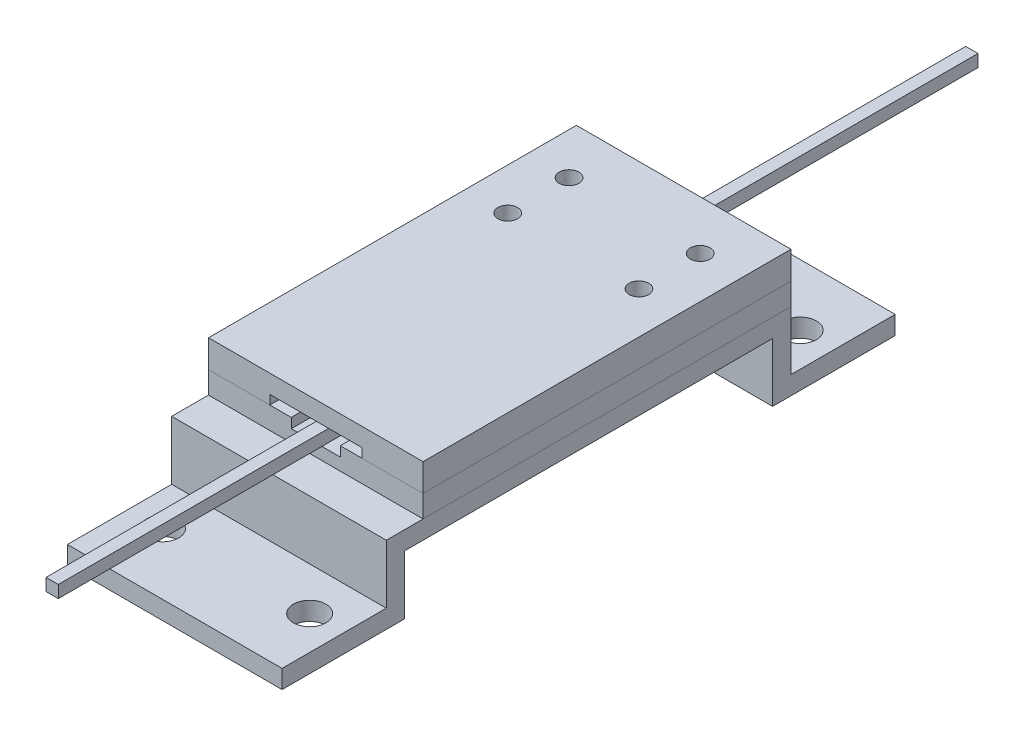
SolidWorks part; units mm, degrees
note: The reader was unsure of these and kept them because the rebuilt part matched: shared geometry of "Sketch5<2>".
ref_plane "Front Plane" through (0, 0, 0) normal (0, 0, 1) x (1, 0, 0)
ref_plane "Top Plane" through (0, 0, 0) normal (0, 1, 0) x (1, 0, 0)
ref_plane "Right Plane" through (0, 0, 0) normal (1, 0, 0) x (0, 0, -1)
sketch "Sketch1" plane through (0, 0, 0) normal (1, 0, 0) x (0, 0, -1)
  line L0 (-33, 3) -> (-50, 3)
  line L1 (-33, 12.6) -> (33, 12.6)
  line L2 (0, 12.6) -> (0, 9.6)
  line L3 (-33, 9.6) -> (33, 9.6)
  line L4 (33, 12.6) -> (33, 9.6)
  line L5 (33, 9.6) -> (30, 9.6)
  line L6 (33, 9.6) -> (33, 0)
  line L7 (33, 0) -> (30, 0)
  line L8 (30, 9.6) -> (30, 0)
  line L9 (33, 0) -> (50, 0)
  line L10 (33, 0) -> (33, 3)
  line L11 (33, 3) -> (50, 3)
  line L12 (50, 0) -> (50, 3)
  line L13 (-50, 0) -> (-50, 3)
  line L14 (-33, 0) -> (-50, 0)
  line L15 (-33, 0) -> (-33, 3)
  line L16 (-33, 0) -> (-30, 0)
  line L17 (-30, 9.6) -> (-30, 0)
  line L18 (-33, 9.6) -> (-30, 9.6)
  line L19 (-33, 9.6) -> (-33, 0)
  line L20 (-33, 12.6) -> (-33, 9.6)
  dimension "D2" = 33
  dimension "D3" = 3
  dimension "D4" = 3
  dimension "D5" = 50
  dimension "D6" = 12.6
extrude "Boss-Extrude1" add sketch "Sketch1" along normal blind 35 contours L1 L20 L3 L2 | L4 L1 L2 L3 | L3 L8 L7 L6 | L9 L12 L11 L6 | L3 L19 L15 L16 L17 | L14 L15 L0 L13
sketch "Sketch2" plane through (0, 12.6, 0) normal (0, 1, 0) x (1, 0, 0)
  line L0 (17.5, 33) -> (17.5, -33) construction
  line L1 (35, 33) -> (0, 33) construction
  line L2 (35, -33) -> (0, -33) construction
  line L4 (6.8, 25) -> (6.8, 15) construction
  line L5 (0, 0) -> (35, 0) construction
  line L6 (35, -33) -> (35, 33) construction
  circle A0 centre (6.8, 25) radius 1.6
  circle A3 centre (28.2, 25) radius 1.6
  circle A4 centre (6.8, 15) radius 1.6
  circle A5 centre (28.2, 15) radius 1.6
  circle A6 centre (5.5, 40) radius 2.65
  circle A7 centre (29.5, 40) radius 2.65
  circle A8 centre (29.5, -40) radius 2.65
  circle A9 centre (5.5, -40) radius 2.65
  circle A10 centre (6.8, 5) radius 1.6
  circle A11 centre (28.2, 5) radius 1.6
  circle A12 centre (6.8, -5) radius 1.6
  circle A13 centre (28.2, -5) radius 1.6
  circle A16 centre (6.8, -25) radius 1.6
  circle A17 centre (28.2, -25) radius 1.6
  circle A18 centre (6.8, -15) radius 1.6 [skipped]
  circle A19 centre (28.2, -15) radius 1.6 [skipped]
  dimension "D1" = 3.2
  dimension "D9" = 5.3
  dimension "D2" = 8
  dimension "D3" = 10.7
  dimension "D7" = 10
  dimension "D8" = 12
  dimension "D10" = 40
  dimension "D6" = 6
extrude "Cut-Extrude1" cut sketch "Sketch2" against normal through all
sketch "Sketch4" plane through (0, 12.6, 0) normal (0, 1, 0) x (1, 0, 0)
  line L0 (35, -33) -> (35, 33) construction
  line L1 (0, 33) -> (35, 33)
  line L2 (0, 33) -> (0, -27)
  line L3 (0, -27) -> (35, -27)
  line L4 (35, 33) -> (35, -27)
  circle A0 centre (6.8, 15) radius 1.6 construction
  circle A1 centre (28.2, 15) radius 1.6 construction
  circle A2 centre (28.2, 25) radius 1.6 construction
  circle A3 centre (6.8, 25) radius 1.6 construction
  circle A4 centre (6.8, 15) radius 1.6
  circle A5 centre (28.2, 15) radius 1.6
  circle A6 centre (28.2, 25) radius 1.6
  circle A7 centre (6.8, 25) radius 1.6
  dimension "D1" = 60
extrude "Boss-Extrude2" add sketch "Sketch4" along normal blind 2 separate body
sketch "Sketch5" plane through (0, 14.6, 0) normal (0, 1, 0) x (1, 0, 0)
  line L0 (0, -27) -> (35, -27) construction
  line L1 (0, 33) -> (13.5, 33)
  line L2 (0, 33) -> (0, -27)
  line L3 (0, -27) -> (13.5, -27)
  line L4 (13.5, 33) -> (13.5, -27)
  line L5 (17.5, 33) -> (17.5, -27) construction
  line L10 (35, 33) -> (0, 33) construction
  line L11 (35, -27) -> (21.5, -27)
  line L12 (21.5, 33) -> (21.5, -27)
  line L13 (35, 33) -> (21.5, 33)
  line L14 (35, 33) -> (35, -27)
  circle A0 centre (6.8, 25) radius 1.6 construction
  circle A1 centre (28.2, 25) radius 1.6 construction
  circle A2 centre (28.2, 15) radius 1.6 construction
  circle A3 centre (6.8, 15) radius 1.6 construction
  circle A4 centre (6.8, 25) radius 1.6
  circle A5 centre (28.2, 25) radius 1.6
  circle A6 centre (28.2, 15) radius 1.6
  circle A7 centre (6.8, 15) radius 1.6
  circle A8 centre (28.2, -25) radius 1.6 construction
  circle A9 centre (6.8, -25) radius 1.6 construction
  circle A10 centre (6.8, -5) radius 1.6 construction
  circle A11 centre (28.2, -5) radius 1.6 construction
  circle A12 centre (28.2, 5) radius 1.6 construction
  circle A13 centre (6.8, 5) radius 1.6 construction
  circle A14 centre (28.2, -25) radius 1.6
  circle A15 centre (6.8, -25) radius 1.6
  circle A16 centre (6.8, -5) radius 1.6
  circle A17 centre (28.2, -5) radius 1.6
  circle A18 centre (28.2, 5) radius 1.6
  circle A19 centre (6.8, 5) radius 1.6
  dimension "D1" = 4
extrude "Boss-Extrude3" add sketch "Sketch5" along normal blind 1.6
sketch "Sketch6" plane through (0, 0, 27) normal (0, 0, 1) x (1, 0, 0)
  line L0 (17.5, 14.6) -> (17.5, 0) construction
  line L1 (0, 16.2) -> (10, 16.2)
  line L2 (0, 16.2) -> (0, 20.7)
  line L3 (0, 20.7) -> (10, 20.7)
  line L4 (10, 16.2) -> (10, 20.7)
  line L5 (13.5, 14.6) -> (21.5, 14.6) construction
  line L6 (35, 0) -> (0, 0) construction
  line L7 (0, 16.2) -> (13.5, 16.2) construction
  line L8 (10, 20.7) -> (25, 20.7)
  line L9 (10, 20.7) -> (10, 17.7)
  line L10 (10, 17.7) -> (25, 17.7)
  line L11 (17.5, 20.7) -> (17.5, 17.7)
  line L13 (35, 20.7) -> (25, 20.7)
  line L14 (25, 16.2) -> (25, 20.7)
  line L15 (35, 16.2) -> (25, 16.2)
  line L16 (35, 16.2) -> (35, 20.7)
  line L17 (25, 20.7) -> (25, 17.7)
  line M12 (35, 16.2) -> (21.5, 16.2)
  line M16 (13.5, 16.2) -> (0, 16.2)
  dimension "D1" = 1.5
  dimension "D2" = 3
  dimension "D3" = 10
extrude "Boss-Extrude4" add sketch "Sketch6" against normal up to surface (60 mm away) separate body contours L16 L13 L14 M12 | L10 L14 L8 L11 | L11 L8 L4 L10 | L4 L3 L2 M16 up to face at (17.5, 14.9, -33)
extrude "Cut-Extrude2" cut sketch "Sketch5<2>" along normal through all
sketch "Sketch5<2>" plane through (0, 14.6, 0) normal (0, 1, 0) x (1, 0, 0) same geometry as "Sketch5"
sketch "Sketch7" plane through (0, 14.6, 0) normal (0, 1, 0) x (1, 0, 0)
  line L0 (0, 0) -> (35, 0) construction
  line L1 (16.5, 80) -> (18.5, 80)
  line L2 (16.5, 80) -> (16.5, -70)
  line L3 (16.5, -70) -> (18.5, -70)
  line L4 (18.5, 80) -> (18.5, -70)
  line L5 (35, 33) -> (35, -27) construction
  point P9 (17.5, 0)
  point P10 (17.5, 80)
  dimension "D1" = 2
  dimension "D2" = 80
  dimension "D3" = 70
extrude "Boss-Extrude5" add sketch "Sketch7" along normal blind 2 separate body
equation "\"D6@Sketch1\"=26.5-(12.9+1)"
equation "\"D3@Sketch2\"=21.4/2"
equation "\"D10@Sketch2\"=80/2"
